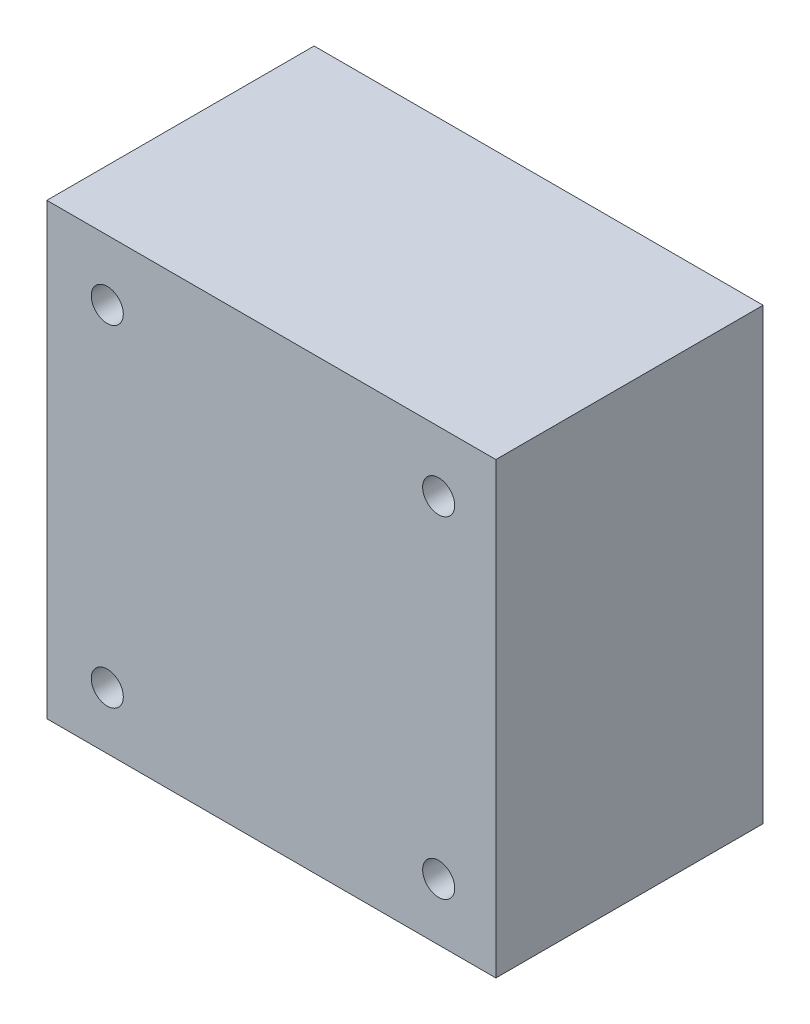
SolidWorks part; units mm, degrees
ref_plane "Front Plane" through (0, 0, 0) normal (0, 0, 1) x (1, 0, 0)
ref_plane "Top Plane" through (0, 0, 0) normal (0, 1, 0) x (1, 0, 0)
ref_plane "Right Plane" through (0, 0, 0) normal (1, 0, 0) x (0, 0, -1)
sketch "Sketch1" plane through (0, 0, 0) normal (0, 0, 1) x (1, 0, 0)
  line L1 (-21, -21) -> (21, -21)
  line L2 (-21, -21) -> (-21, 21)
  line L3 (-21, 21) -> (21, 21)
  line L4 (21, -21) -> (21, 21)
  line L5 (-21, -21) -> (21, 21) construction
  line L6 (-21, 21) -> (21, -21) construction
  point P0 (0, 0)
  dimension "D1" = 42
  dimension "D2" = 42
extrude "Boss-Extrude1" add sketch "Sketch1" along normal blind 25
sketch "Sketch2" plane through (0, 0, 25) normal (0, 0, 1) x (1, 0, 0)
  circle A0 centre (15.65, 15.35) radius 1.5
  circle A1 centre (-15.35, 15.35) radius 1.5
  circle A2 centre (-15.35, -15.65) radius 1.5
  circle A3 centre (15.65, -15.65) radius 1.5
  dimension "D1" = 3
  dimension "D2" = 3
  dimension "D3" = 3
  dimension "D4" = 3
extrude "Cut-Extrude1" cut sketch "Sketch2" against normal through all
